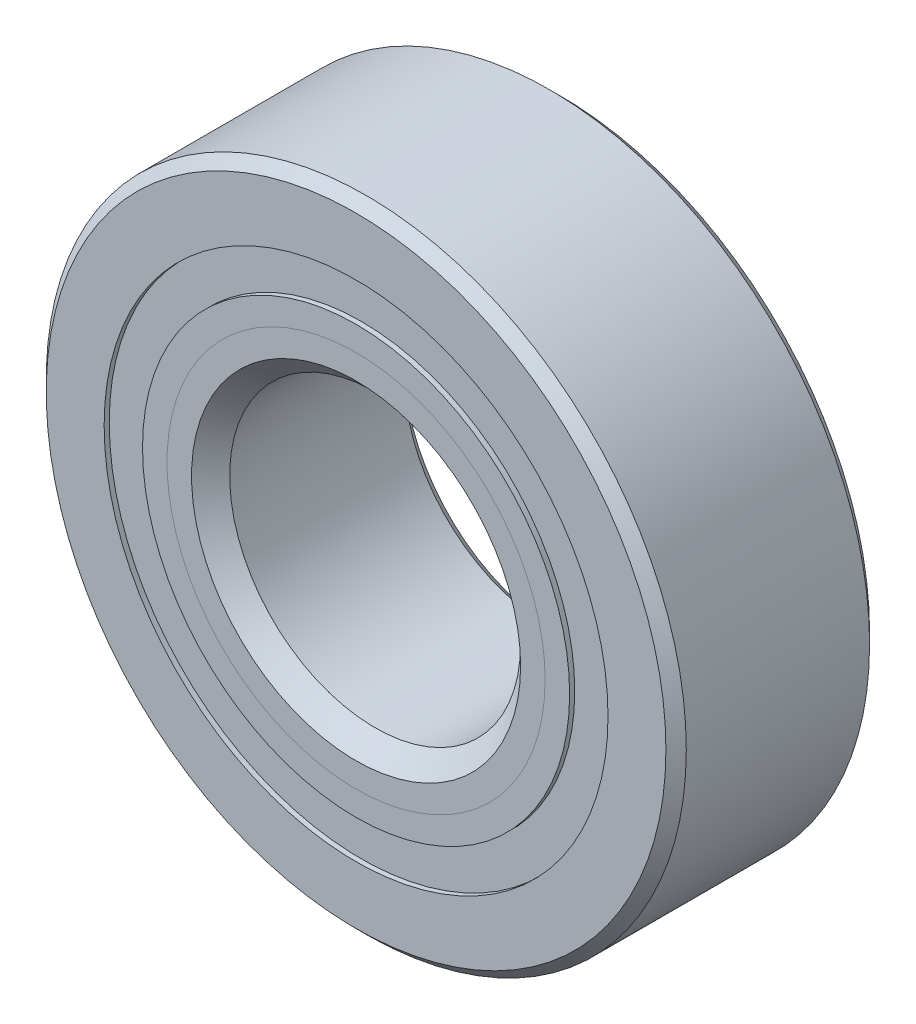
SolidWorks part; units mm, degrees
ref_plane "Front Plane" through (0, 0, 0) normal (0, 0, 1) x (1, 0, 0)
ref_plane "Top Plane" through (0, 0, 0) normal (0, 1, 0) x (1, 0, 0)
ref_plane "Right Plane" through (0, 0, 0) normal (1, 0, 0) x (0, 0, -1)
sketch "Sketch1" plane through (0, 0, 0) normal (1, 0, 0) x (0, 0, -1)
  line L0 (-5.5562, 0) -> (5.5562, 0) construction
  line L1 (0, 17.4625) -> (0, -17.4625) construction
  line L2 (5.0006, 17.4625) -> (-5.0006, 17.4625)
  line L3 (-5.0006, 17.4625) -> (-5.5563, 16.9069)
  line L4 (-5.5563, 16.9069) -> (-5.5563, 13.7467)
  line L5 (-5.5563, 13.7467) -> (-2.4694, 13.7467)
  line L6 (5.5563, 13.7467) -> (2.4694, 13.7467)
  line L7 (5.5563, 16.9069) -> (5.5563, 13.7467)
  line L8 (5.0006, 17.4625) -> (5.5563, 16.9069)
  line L9 (0, 17.4625) -> (0, 12.7) construction
  line L10 (0, 12.7) -> (0, 7.9375) construction
  arc A0 (-2.4694, 13.7467) -> (2.4694, 13.7467) centre (0, 12.7) cw
  point P14 (0, 7.9375)
  dimension "D3" = 4.9389
  dimension "D1" = 45
  dimension "Width" = 11.1125
  dimension "OD" = 34.925
  dimension "D2" = 0.5556
  dimension "Shaft Dia" = 15.875
  dimension "D4" = 1.0467
revolve "Revolve1" add sketch "Sketch1" angle 360 about L0
sketch "Sketch2" plane through (0, 0, 0) normal (1, 0, 0) x (0, 0, -1)
  line L0 (-5.5563, 11.6533) -> (-2.4694, 11.6533)
  line L1 (-5.5563, 16.9069) -> (-5.5563, -16.9069) construction
  line L2 (-5.5563, 11.6533) -> (-5.5563, 10.3155)
  line L3 (-5.5563, 10.3155) -> (-4.2184, 8.9777)
  line L4 (-4.2184, 8.9777) -> (0, 8.9777)
  line L5 (0, 17.4625) -> (0, -17.4625) construction
  line L6 (0, 8.9777) -> (0, 10.0179)
  line L7 (0, 10.0179) -> (0, 7.9375) construction
  line L8 (-5.5563, 11.6533) -> (-5.5563, 8.9777) construction
  line L9 (-5.5563, 8.9777) -> (-4.2184, 8.9777) construction
  arc A0 (-2.4694, 11.6533) -> (0, 10.0179) centre (0, 12.7) ccw
  arc A1 (2.4694, 13.7467) -> (-2.4694, 13.7467) centre (0, 12.7) ccw construction
  circle A2 centre (0, 12.7) radius 2.6821 construction
  dimension "D1" = 45
revolve "Revolve2" add sketch "Sketch2" angle 360 about L0
sketch "Sketch3" plane through (0, 0, 0) normal (1, 0, 0) x (0, 0, -1)
  line L0 (-5.5563, 10.3155) -> (-4.2184, 8.9777)
  line L1 (-4.2184, 8.9777) -> (0, 8.9777)
  line L2 (0, 8.9777) -> (0, 10.0179)
  line L3 (-5.5563, 10.3155) -> (-5.5563, 8.9777)
  line L4 (-5.5563, 11.6533) -> (-5.5563, 8.9777) construction
  line L5 (-5.5563, 8.9777) -> (-4.5161, 7.9375)
  line L6 (-4.5161, 7.9375) -> (5.0006, 7.9375)
  line L7 (5.0006, 17.4625) -> (5.0006, -17.4625) construction
  line L8 (5.0006, 7.9375) -> (5.5563, 8.4931)
  line L9 (5.5563, -16.9069) -> (5.5563, 16.9069) construction
  line L10 (5.5563, 8.4931) -> (5.5563, 11.6533)
  line L11 (5.5563, 11.6533) -> (2.4694, 11.6533)
  line L13 (5.0006, 17.4625) -> (5.5563, 16.9069) construction
  circle A0 centre (0, 12.7) radius 2.6821 construction
  arc A1 (2.4694, 11.6533) -> (0, 10.0179) centre (0, 12.7) cw
revolve "Revolve3" add sketch "Sketch3" angle 360 about L0
sketch "Sketch4" plane through (0, 0, 0) normal (1, 0, 0) x (0, 0, -1)
  line L0 (-2.6821, 12.7) -> (2.6821, 12.7)
  circle A1 centre (0, 12.7) radius 2.6821 construction
  arc A2 (-2.6821, 12.7) -> (2.6821, 12.7) centre (0, 12.7) cw
  arc A3 (2.4694, 13.7467) -> (-2.4694, 13.7467) centre (0, 12.7) ccw construction
revolve "Revolve4" add sketch "Sketch4" angle 360 about L0
ref_axis "Axis1" through (0, 0, -5.5562) along (0, 0, 1)
pattern_circular "CirPattern1" count 12 every 30 about axis through (0, 0, -5.5562) along (0, 0, 1) of bodies 104
sketch "Sketch5" plane through (0, 0, 0) normal (1, 0, 0) x (0, 0, -1)
  line L0 (-5.5563, 13.7467) -> (-2.4694, 13.7467) construction
  line L1 (-5.2784, 13.7467) -> (-2.6821, 13.7467)
  line L2 (-5.2784, 13.7467) -> (-5.2784, 11.6533)
  line L3 (-5.2784, 11.6533) -> (-2.6821, 11.6533)
  line L4 (-2.6821, 13.7467) -> (-2.6821, 11.6533)
  line L5 (-5.5563, 11.6533) -> (-2.4694, 11.6533) construction
  line L6 (-5.0006, 17.4625) -> (-5.5563, 16.9069) construction
  line L7 (0, 17.4625) -> (0, 7.9375) construction
  line L8 (5.2784, 11.6533) -> (2.6821, 11.6533)
  line L9 (2.6821, 13.7467) -> (2.6821, 11.6533)
  line L10 (5.2784, 13.7467) -> (2.6821, 13.7467)
  line L11 (5.2784, 13.7467) -> (5.2784, 11.6533)
  circle A0 centre (0, 12.7) radius 2.6821 construction
  point P10 (-5.2784, 17.1847)
revolve "Revolve5" add sketch "Sketch5" angle 360 about L0
equation "\"D2@Sketch1\" = \"Width@Sketch1\"*.05"
equation "\"D3@Sketch1\" = \"Width@Sketch1\"/2.25"
equation "\"D4@Sketch1\" = (((\"OD@Sketch1\"-\"Width@Sketch1\")/2)/3.25)/3.5"
equation "\"D2@CirPattern1\" = 360/\"Balls@CirPattern1\""
